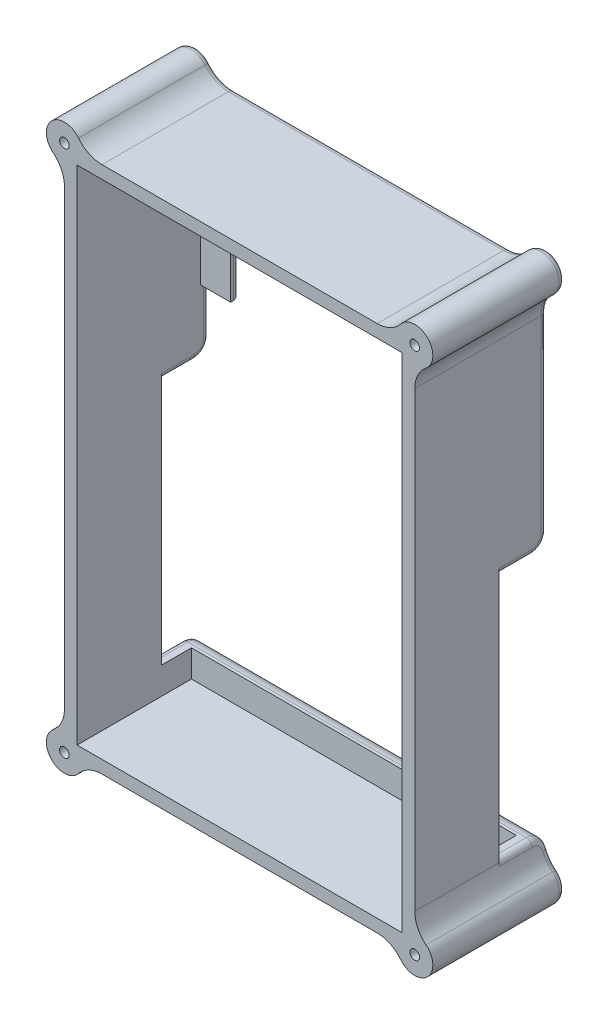
SolidWorks part; units mm, degrees
ref_plane "Front Plane" through (0, 0, 0) normal (0, 0, 1) x (1, 0, 0)
ref_plane "Top Plane" through (0, 0, 0) normal (0, 1, 0) x (1, 0, 0)
ref_plane "Right Plane" through (0, 0, 0) normal (1, 0, 0) x (0, 0, -1)
sketch "Sketch1" plane through (0, 0, 0) normal (0, 0, 1) x (1, 0, 0)
  line L0 (54, 167) -> (54, 161)
  line L1 (0, 0) -> (108, 0)
  line L2 (0, 0) -> (0, 167)
  line L3 (0, 167) -> (108, 167)
  line L4 (108, 0) -> (108, 167)
  line L5 (0, 0) -> (108, 0)
  line L6 (0, 0) -> (0, 9)
  line L7 (0, 9) -> (108, 9)
  line L8 (108, 0) -> (108, 9)
  line L9 (54, 161) -> (69, 161)
  line L10 (54, 161) -> (39, 161)
  line L11 (39, 167) -> (39, 157)
  line L12 (69, 167) -> (69, 157)
  line L13 (108, 157) -> (98, 157) construction
  line L14 (98, 157) -> (69, 157)
  line L15 (0, 157) -> (10, 157) construction
  line L16 (39, 157) -> (10, 157)
  line L17 (10, 157) -> (10, 112)
  line L18 (10, 112) -> (0, 112)
  line L19 (98, 157) -> (98, 112)
  line L20 (98, 112) -> (108, 112)
  line L21 (0, 167) -> (-10.2204, 177.2204)
  line L22 (108, 167) -> (111.6525, 170.6525)
  line L23 (0, 0) -> (-4.2426, -4.2426)
  line L24 (108, 0) -> (112.2426, -4.2426)
  line L25 (-4.2426, -4.2426) -> (-4.2426, 171.2426)
  line L26 (-4.2426, 171.2426) -> (112.2426, 171.2426)
  line L27 (112.2426, 171.2426) -> (112.2426, -4.2426)
  line L28 (-4.2426, -4.2426) -> (112.2426, -4.2426)
  line L29 (0, 9) -> (-4.2426, 9)
  line L30 (108, 9) -> (112.2426, 9)
  line L31 (108, 91) -> (112.2426, 91)
  line L32 (0, 91) -> (-4.2426, 91)
  circle A0 centre (-4.2426, 171.2426) radius 6
  circle A1 centre (-4.2426, 171.2426) radius 1.6
  circle A2 centre (112.2426, 171.2426) radius 6
  circle A3 centre (112.2426, 171.2426) radius 1.6
  circle A4 centre (-4.2426, -4.2426) radius 6
  circle A5 centre (-4.2426, -4.2426) radius 1.6
  circle A6 centre (112.2426, -4.2426) radius 6
  circle A7 centre (112.2426, -4.2426) radius 1.6
  dimension "D4" = 12
  dimension "D5" = 12
  dimension "D6" = 82
  dimension "D7" = 3.2
  dimension "D8" = 3.2
  dimension "D9" = 3.2
  dimension "D10" = 3.2
  dimension "D1" = 167
  dimension "D2" = 108
  dimension "D3" = 9
extrude "Boss-Extrude1" add sketch "Sketch1" along normal blind 3 contours L18 L17 L16 L11 L3 L2 | L19 L20 L4 L3 L12 L14 | L12 L3 L0 L9 | L3 L11 L10 L0 region at (61.5, 164, 0) region at (46.5, 164, 0) region at (38.3258, 164, 0) region at (88.5, 166.3258, 0)
extrude "Boss-Extrude2" add sketch "Sketch1<3>" along normal blind 6 separate body contours L7 L2 L1 L4 region at (54, 4.5, 0)
sketch "Sketch1<3>" plane through (0, 0, 0) normal (0, 0, 1) x (1, 0, 0) same geometry as "Sketch1"
extrude "Boss-Extrude3" add sketch "Sketch1<4>" along normal blind 44 contours A4 L2 A0 L25 | A5 L23 A4 L25 | A5 L28 A4 L23 | A5 L25 A4 L28 | A6 L1 A4 L28 | A7 L24 A6 L28 | A7 L27 A6 L24 | A6 L27 A2 L4 | A7 L28 A6 L27 | A3 L26 A2 L22 | A3 L22 A2 L27 | A3 L27 A2 L26 | A2 L26 A0 L3 | A1 L21 A0 L26 | A1 L25 A0 L21 | A1 L21 A0 L25 | A1 L26 A0 L21 | A4 L2 L29 L25 | A6 L27 L30 L4 | L2 L32 L25 L29 | L31 L4 L30 L27 region at (54, 169.11, 0) region at (-2.6672, 167.4392, 0) region at (-0.4392, 169.6672, 0) region at (-2.1133, 128.3963, 0) region at (110.1133, 128.3963, 0) region at (108.4392, 169.6672, 0) region at (110.6672, 167.4392, 0) region at (-2.9748, 174.3034, 0) region at (-7.3034, 169.9748, 0) region at (112.2426, 177.0729, 0) region at (-2.1213, 50, 0) region at (110.1213, 50, 0) region at (-2.0445, 5.0888, 0) region at (110.0445, 5.0888, 0) region at (-0.4392, -2.6672, 0) region at (54, -2.11, 0) region at (-2.6672, -0.4392, 0) region at (-4.4123, -0.4426, 0) region at (110.6672, -0.4392, 0) region at (108.4392, -2.6672, 0) region at (116.3653, -0.12, 0)
sketch "Sketch1<4>" plane through (0, 0, 0) normal (0, 0, 1) x (1, 0, 0) same geometry as "Sketch1"
extrude "Cut-Extrude1" cut sketch "Sketch1<6>" along normal blind 16 contours L2 L32 L25 L29 | L31 L4 L30 L27 region at (-2.1213, 50, 0) region at (110.1213, 50, 0)
sketch "Sketch1<6>" plane through (0, 0, 0) normal (0, 0, 1) x (1, 0, 0) same geometry as "Sketch1"
fillet "Fillet1" radius 10 8 edges at (106.2426, 171.2426, 22) (1.7574, 171.2426, 22) (-4.2426, 165.2426, 22) (-4.2426, 1.7574, 22) (1.7574, -4.2426, 22) (106.2426, -4.2426, 22) (112.2426, 1.7574, 22) (112.2426, 165.2426, 22)
fillet "Fillet2" radius 5 3 edges at (110.1213, 91, 0) (-2.1213, 91, 0) (54, 9, 0)
fillet "Fillet3" radius 2 43 edges at (112.2426, 9, 10.5) (112.3333, 6.9038, 0.9296) (-4.2426, 9, 10.5) (-4.5423, 5.8178, 0.3422) (0, 91, 10.5) (0, 92.4645, 1.4645) (108, 91, 10.5) (108, 92.4645, 1.4645) (-4.2426, 91, 10.5) (-4.2426, 92.4645, 1.4645) (112.2426, 91, 10.5) (112.2426, 92.4645, 1.4645) (-2.6426, -4.2426, 0) (113.8426, -4.2426, 0) (-8.4853, -8.4853, 0) (3.9172, -5.2288, 0) (54, -4.2426, 0) (104.0828, -5.2288, 0) (116.4853, -8.4853, 0) (114.3869, 2.0597, 0) (-6.3869, 2.0597, 0) (113.2288, 163.0828, 0) (116.4853, 175.4853, 0) (104.0828, 172.2288, 0) (54, 171.2426, 0) (3.9172, 172.2288, 0) (-8.4853, 175.4853, 0) (-5.2288, 163.0828, 0) (-4.2426, 127.3763, 0) (0, 104, 0) (5, 112, 0) (10, 134.5, 0) (24.5, 157, 0) (39, 159, 0) (54, 161, 0) (69, 159, 0) (83.5, 157, 0) (98, 134.5, 0) (103, 112, 0) (108, 104, 0) (112.2426, 127.3763, 0) (-2.6426, 171.2426, 0) (113.8426, 171.2426, 0)
